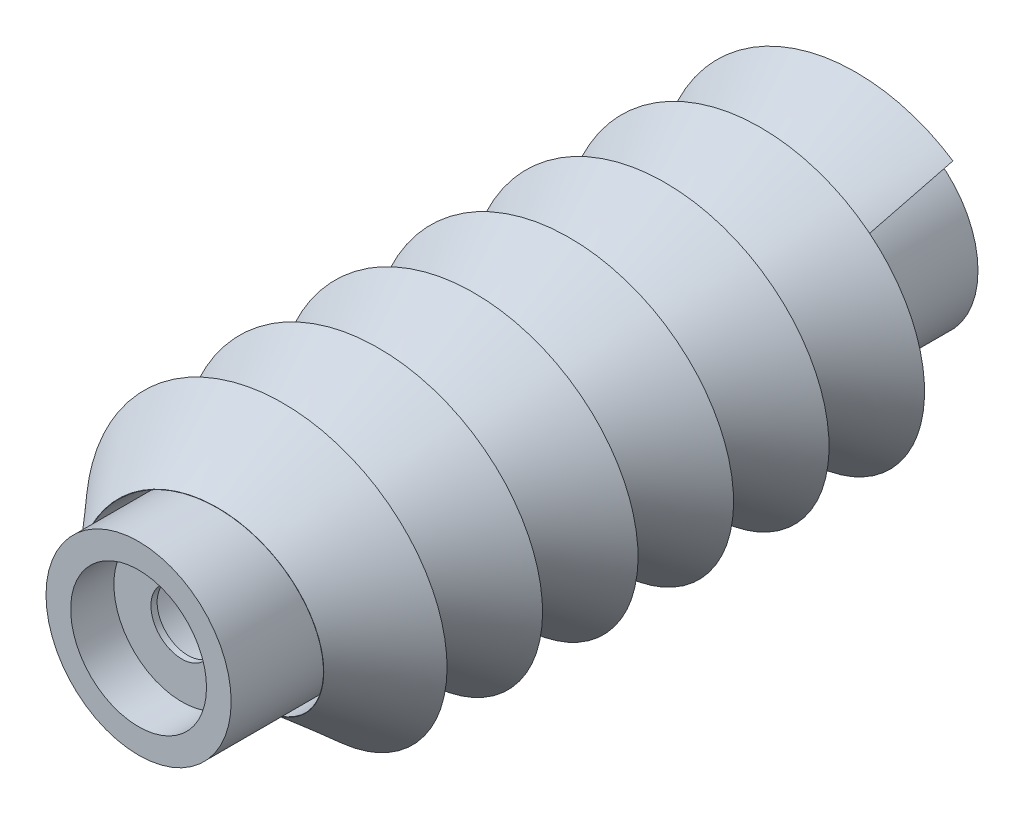
SolidWorks part; units mm, degrees
ref_plane "Спереди" through (0, 0, 0) normal (0, 0, 1) x (1, 0, 0)
ref_plane "Сверху" through (0, 0, 0) normal (0, 1, 0) x (1, 0, 0)
ref_plane "Справа" through (0, 0, 0) normal (1, 0, 0) x (0, 0, -1)
sketch "Эскиз1" plane through (0, 0, 0) normal (0, 0, 1) x (1, 0, 0)
  circle A0 centre (0, 0) radius 15
  circle A1 centre (0, 0) radius 11
  dimension "D1" = 22
  dimension "D2" = 30
extrude "Бобышка-Вытянуть1" add sketch "Эскиз1" along normal blind 63
sketch "Эскиз6" plane through (0, 0, 0) normal (0, 0, -1) x (-1, 0, 0)
  circle A0 centre (0, 0) radius 15 construction
  circle A1 centre (0, 0) radius 15
curve "Спираль1" pitch 15.4738 height 100.58 turns 6.5
ref_plane "Плоскость1" through (9.4398, 11.6572, 0) normal (-0.7669, 0.621, 0.162) x (0.119, -0.1105, 0.9867)
sketch "Эскиз7" plane through (9.4398, 11.6572, 0) normal (-0.7669, 0.621, 0.162) x (0.119, -0.1105, 0.9867)
  line L1 (0, 0) -> (16.3362, 0.9182)
  line L2 (0, 0) -> (5.6542, 10.3336)
  line L3 (5.6542, 10.3336) -> (16.3362, 0.9627)
  line L4 (16.3362, 0.9182) -> (16.3362, 0.9627)
  dimension "D1" = 16.3362
  dimension "D2" = 10
sweep "По траектории1" add profiles "Эскиз7" path "Спираль1"
sketch "Эскиз12" plane through (0, 0, 63) normal (0, 0, 1) x (1, 0, 0)
  circle A1 centre (0, 0) radius 15
  circle A2 centre (0, 0) radius 15
  dimension "D1" = 0
extrude "Бобышка-Вытянуть2" add sketch "Эскиз12" along normal blind 8
hole_wizard "Отверстие1" positions "Эскиз22" profile "Эскиз21" legacy
sketch "Эскиз22" plane through (0, 0, 71) normal (0, 0, 1) x (1, 0, 0)
  point P0 (0, 0)
  point P2 (0, 0)
  point P3 (0, 0)
sketch "Эскиз21" plane through (0, 0, 71) normal (1, 0, 0) x (0, -1, 0)
  line L0 (0, 0) -> (0, 7)
  line L1 (0, 7) -> (11.005, 7)
  line L2 (11.005, 7) -> (11.005, 0)
  line L3 (11.005, 0) -> (0, 0)
  line L4 (0, 110) -> (0, -10) construction
  point P2 (0, 7)
  point P7 (0, 7)
  dimension "Диаметр" = 22.01
  dimension "Глубина" = 7
sketch "Эскиз34" plane through (0, 0, 0) normal (0, 0, -1) x (-1, 0, 0)
  circle A1 centre (0, 0) radius 15
  circle A2 centre (0, 0) radius 15
  dimension "D1" = 0
extrude "Бобышка-Вытянуть6" add sketch "Эскиз34" along normal blind 60
move or copy body "Тело-Переместить/Копировать1" bodies to move or copy 104 copy no translate (0, 0, -50)
hole_wizard "Отверстие2" positions "Эскиз36" profile "Эскиз35" legacy
sketch "Эскиз36" plane through (0, 0, -60) normal (0, 0, -1) x (-1, 0, 0)
  point P0 (0, 0)
sketch "Эскиз35" plane through (0, 0, -60) normal (1, 0, 0) x (0, 1, 0)
  line L0 (0, 0) -> (0, 50)
  line L1 (0, 50) -> (14, 50)
  line L2 (14, 50) -> (14, 0)
  line L3 (14, 0) -> (0, 0)
  line L4 (0, 110) -> (0, -10) construction
  dimension "Диаметр" = 28
  dimension "Глубина" = 50
sketch "Эскиз43" plane through (0, 0, -10) normal (0, 0, -1) x (-1, 0, 0)
  line L2 (0.58, 1.9141) -> (0.58, -1.9141)
  arc A0 (0.58, 1.9141) -> (0.58, -1.9141) centre (0, 0) ccw
  dimension "D2" = 4
  dimension "D3" = 0.58
extrude "Вырез-Вытянуть2" cut sketch "Эскиз43" against normal blind 10 contours L2 A0
other "Переместить грань1" face at (-14, 0, -60) parameters "D1"=10
hole_wizard "Отверстие3" positions "Эскиз45" profile "Эскиз44" legacy
sketch "Эскиз45" plane through (0, 0, 64) normal (0, 0, 1) x (1, 0, 0)
  point P0 (0, 0)
  point P1 (0, 0)
  point P3 (0, 0)
  point P4 (0, 0)
sketch "Эскиз44" plane through (0, 0, 64) normal (1, 0, 0) x (0, -1, 0)
  line L0 (0, 0) -> (0, 20)
  line L1 (0, 20) -> (5, 20)
  line L2 (5, 20) -> (5, 0)
  line L3 (5, 0) -> (0, 0)
  line L4 (0, 110) -> (0, -10) construction
  dimension "Диаметр" = 10
  dimension "Глубина" = 20
